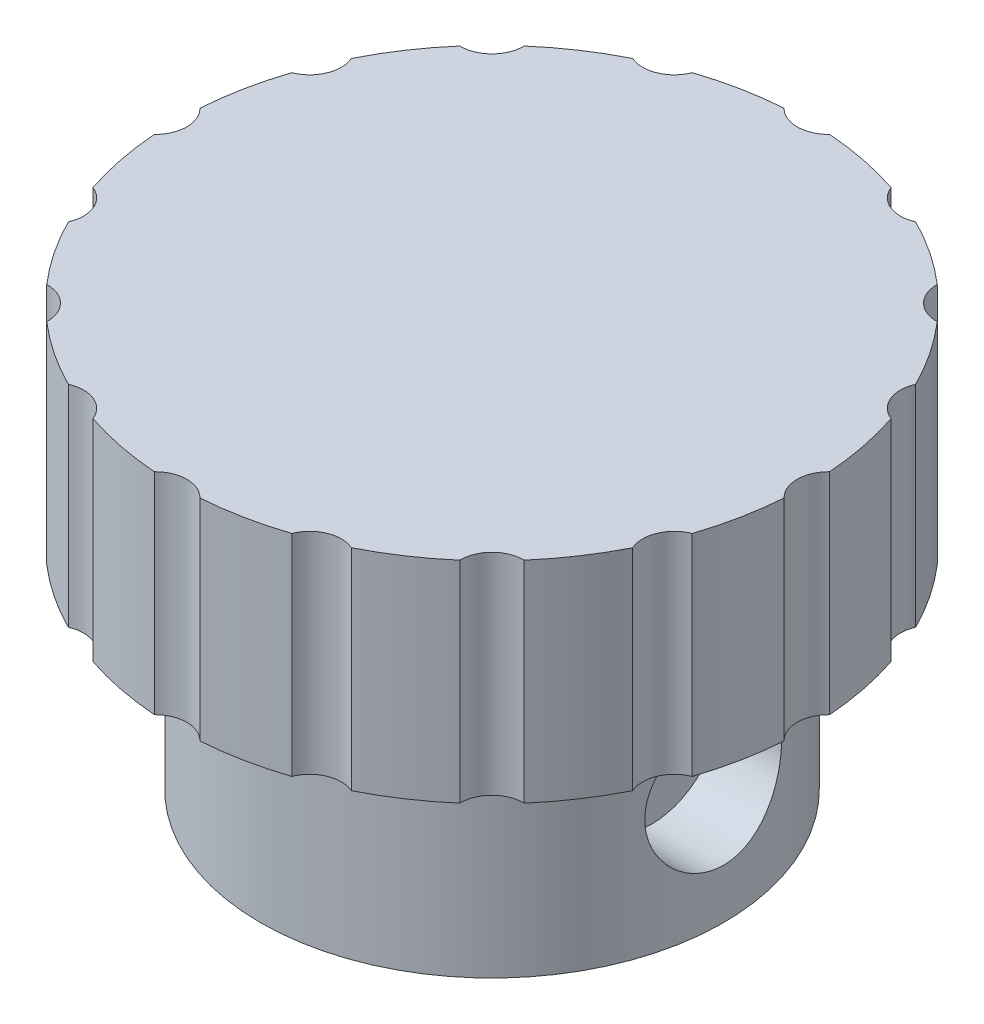
SolidWorks part; units mm, degrees
material "Benutzerdefinierter Kunststoff"
ref_plane "Front Plane" through (0, 0, 0) normal (0, 0, 1) x (1, 0, 0)
ref_plane "Top Plane" through (0, 0, 0) normal (0, 1, 0) x (1, 0, 0)
ref_plane "Right Plane" through (0, 0, 0) normal (1, 0, 0) x (0, 0, -1)
sketch "Sketch1" plane through (0, 0, 0) normal (0, 1, 0) x (1, 0, 0)
  line L1 (0, -5.7735) -> (5, -2.8868)
  line L2 (5, -2.8868) -> (5, 2.8868)
  line L3 (5, 2.8868) -> (0, 5.7735)
  line L4 (0, 5.7735) -> (-5, 2.8868)
  line L5 (-5, 2.8868) -> (-5, -2.8868)
  line L6 (-5, -2.8868) -> (0, -5.7735)
  circle A0 centre (0, 0) radius 5 construction
  circle A1 centre (0, 0) radius 11
  arc A2 (-1.0818, 14.9609) -> (-4.7258, 14.2361) centre (0, 0) ccw
  arc A3 (-1.0818, 14.9609) -> (1.0818, 14.9609) centre (0, 16) ccw
  arc A4 (4.7258, 14.2361) -> (6.7248, 13.4081) centre (6.1229, 14.7821) ccw
  arc A5 (9.814, 11.3439) -> (11.3439, 9.814) centre (11.3137, 11.3137) ccw
  arc A6 (13.4081, 6.7248) -> (14.2361, 4.7258) centre (14.7821, 6.1229) ccw
  arc A7 (14.9609, 1.0818) -> (14.9609, -1.0818) centre (16, 0) ccw
  arc A8 (14.2361, -4.7258) -> (13.4081, -6.7248) centre (14.7821, -6.1229) ccw
  arc A9 (11.3439, -9.814) -> (9.814, -11.3439) centre (11.3137, -11.3137) ccw
  arc A10 (6.7248, -13.4081) -> (4.7258, -14.2361) centre (6.1229, -14.7821) ccw
  arc A11 (1.0818, -14.9609) -> (-1.0818, -14.9609) centre (0, -16) ccw
  arc A12 (-4.7258, -14.2361) -> (-6.7248, -13.4081) centre (-6.1229, -14.7821) ccw
  arc A13 (-9.814, -11.3439) -> (-11.3439, -9.814) centre (-11.3137, -11.3137) ccw
  arc A14 (-13.4081, -6.7248) -> (-14.2361, -4.7258) centre (-14.7821, -6.1229) ccw
  arc A15 (-14.9609, -1.0818) -> (-14.9609, 1.0818) centre (-16, 0) ccw
  arc A16 (-14.2361, 4.7258) -> (-13.4081, 6.7248) centre (-14.7821, 6.1229) ccw
  arc A17 (-11.3439, 9.814) -> (-9.814, 11.3439) centre (-11.3137, 11.3137) ccw
  arc A18 (-6.7248, 13.4081) -> (-4.7258, 14.2361) centre (-6.1229, 14.7821) ccw
  arc A19 (4.7258, 14.2361) -> (1.0818, 14.9609) centre (0, 0) ccw
  arc A20 (9.814, 11.3439) -> (6.7248, 13.4081) centre (0, 0) ccw
  arc A21 (13.4081, 6.7248) -> (11.3439, 9.814) centre (0, 0) ccw
  arc A22 (14.9609, 1.0818) -> (14.2361, 4.7258) centre (0, 0) ccw
  arc A23 (14.2361, -4.7258) -> (14.9609, -1.0818) centre (0, 0) ccw
  arc A24 (11.3439, -9.814) -> (13.4081, -6.7248) centre (0, 0) ccw
  arc A25 (6.7248, -13.4081) -> (9.814, -11.3439) centre (0, 0) ccw
  arc A26 (1.0818, -14.9609) -> (4.7258, -14.2361) centre (0, 0) ccw
  arc A27 (-4.7258, -14.2361) -> (-1.0818, -14.9609) centre (0, 0) ccw
  arc A28 (-9.814, -11.3439) -> (-6.7248, -13.4081) centre (0, 0) ccw
  arc A29 (-13.4081, -6.7248) -> (-11.3439, -9.814) centre (0, 0) ccw
  arc A30 (-14.9609, -1.0818) -> (-14.2361, -4.7258) centre (0, 0) ccw
  arc A31 (-14.2361, 4.7258) -> (-14.9609, 1.0818) centre (0, 0) ccw
  arc A32 (-11.3439, 9.814) -> (-13.4081, 6.7248) centre (0, 0) ccw
  arc A33 (-6.7248, 13.4081) -> (-9.814, 11.3439) centre (0, 0) ccw
  dimension "D1" = 10
  dimension "D2" = 16
  dimension "D3" = 16
extrude "Boss-Extrude1" add sketch "Sketch1" along normal blind 10 contours A31 A15 A30 A14 A29 A13 A28 A12 A27 A11 A26 A10 A25 A9 A24 A8 A23 A7 A22 A6 A21 A5 A20 A4 A19 A3 A2 A18 A33 A17 A32 A16
extrude "Boss-Extrude2" add sketch "Sketch1<3>" against normal blind 10 from surface contours A1 starting at face at (0, 0, 0)
sketch "Sketch1<3>" plane through (0, 0, 0) normal (0, 1, 0) x (1, 0, 0) same geometry as "Sketch1"
sketch "Skizze1" plane through (0, -10, 0) normal (0, -1, 0) x (1, 0, 0)
  line L0 (1.9, 2.4495) -> (1.9, -2.4495)
  line L1 (0, 0) -> (-3.1, 0) construction
  arc A0 (1.9, 2.4495) -> (1.9, -2.4495) centre (0, 0) ccw
  dimension "D1" = 6.2
  dimension "4,7" = 5
extrude "Schnitt-Linear austragen1" cut sketch "Skizze1" against normal blind 10
ref_plane "Ebene1" through (11, 0, 0) normal (1, 0, 0) x (0, 1, 0)
hole_wizard "Stirnsenkung für M3 Zylinderschraube mit Innensechskant1" positions "Skizze4" profile "Skizze6" counterbore size "M3" standard "DIN" end condition up to next
sketch "Skizze4" plane through (11, 0, 0) normal (1, 0, 0) x (0, 1, 0)
  point P0 (-4.3869, 0)
sketch "Skizze6" plane through (11, -4.3869, 0) normal (0, 1, 0) x (0, 0, -1)
  line L0 (0, 0) -> (0, 9.1)
  line L1 (0, 9.1) -> (1.4, 9.1)
  line L3 (1.4, 9.1) -> (1.4, 3.4)
  line L4 (1.4, 3.4) -> (3.25, 3.4)
  line L5 (3.25, 3.4) -> (3.25, 0)
  line L7 (3.25, 0) -> (0, 0)
  line L11 (0, -6.35) -> (0, 107.95) construction
  dimension "Bohrerdurchmesser" = 2.8
  dimension "Bohrungstiefe" = 9.1
  dimension "Senkdurchmesser2" = 6.5
  dimension "Senktiefe2" = 3.4
